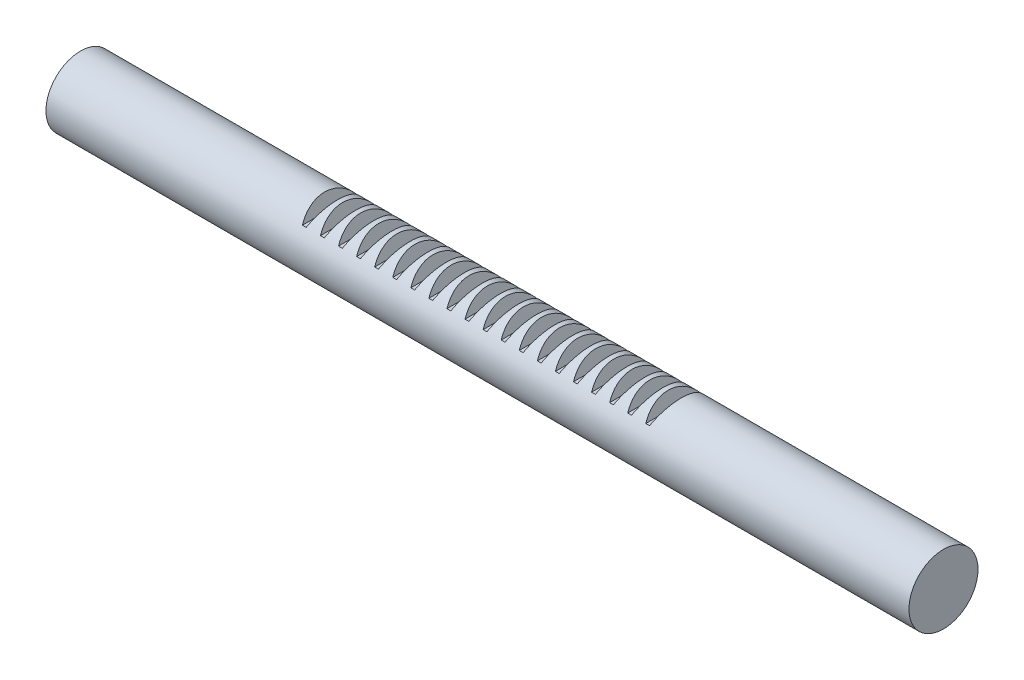
SolidWorks part; units mm, degrees
ref_plane "Front Plane" through (0, 0, 0) normal (0, 0, 1) x (1, 0, 0)
ref_plane "Top Plane" through (0, 0, 0) normal (0, 1, 0) x (1, 0, 0)
ref_plane "Right Plane" through (0, 0, 0) normal (1, 0, 0) x (0, 0, -1)
sketch "Sketch1" plane through (0, 0, 0) normal (1, 0, 0) x (0, 0, -1)
  circle A0 centre (0, 0) radius 12
  dimension "D1" = 24
extrude "Boss-Extrude1" add sketch "Sketch1" along normal blind 150 and the other way blind 150
sketch "Sketch2" plane through (0, 0, 0) normal (0, 0, 1) x (1, 0, 0)
  line L1 (150, 12) -> (-150, 12) construction
  line L2 (-62.171, 7.5) -> (-63.4927, 7.5)
  line L3 (-63.4927, 7.5) -> (-65.1306, 12)
  line L4 (-65.1306, 12) -> (-60.5331, 12)
  line L5 (-62.171, 7.5) -> (-60.5331, 12)
  line L6 (-64.4026, 10) -> (-61.2611, 10) construction
  line L7 (-62.8319, 12) -> (-62.8319, 7.5) construction
  line L8 (-62.8319, 12) -> (-62.8319, 14) construction
  dimension "D5" = 62.8319
  dimension "D4" = 2
  dimension "D2" = 2.5
  dimension "D3" = 2
  dimension "D6" = 20
  dimension "D1" = 3.1416
extrude "Cut-Extrude1" cut sketch "Sketch2" against normal through all and the other way through all
pattern_linear "LPattern1" count 20 spacing 6.2832 along (1, 0, 0) of "Cut-Extrude1"
equation "\"D1@Sketch2\"= pi * \"D4@Sketch2\" / 2mm"
equation "\"D3@Sketch2\"= \"D4@Sketch2\""
equation "\"D2@Sketch2\"= 1.25 * \"D4@Sketch2\""
equation "\"D3@LPattern1\"= pi * \"D4@Sketch2\""
equation "\"D5@Sketch2\"= pi * \"D4@Sketch2\" * \"D1@LPattern1\" / 2mm"
